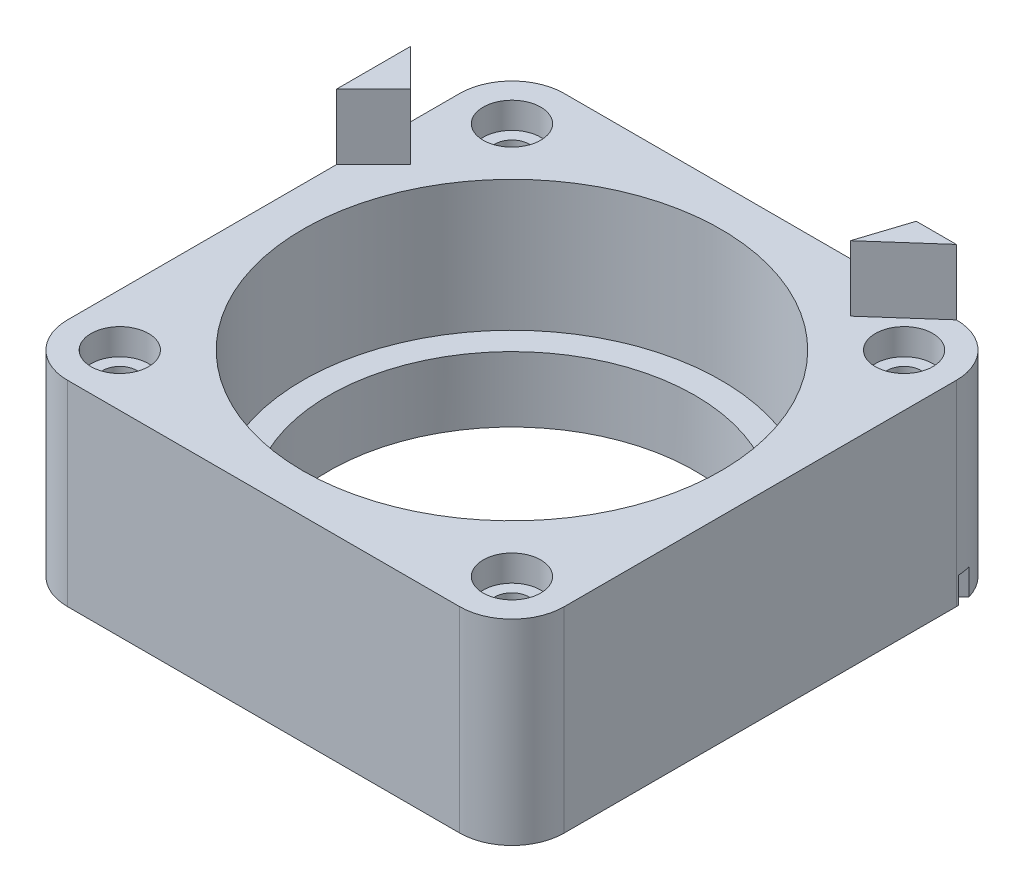
SolidWorks part; units mm, degrees
material "ABS"
ref_plane "Front Plane" through (0, 0, 0) normal (0, 0, 1) x (1, 0, 0)
ref_plane "Top Plane" through (0, 0, 0) normal (0, 1, 0) x (1, 0, 0)
ref_plane "Right Plane" through (0, 0, 0) normal (1, 0, 0) x (0, 0, -1)
sketch "Sketch1" plane through (0, 0, 0) normal (0, 1, 0) x (1, 0, 0)
  line L0 (19, 19) -> (-19, 19)
  line L1 (-19, 19) -> (-19, -19)
  line L2 (-19, -19) -> (19, -19)
  line L3 (19, -19) -> (19, 19)
  line L4 (-19, 19) -> (19, -19) construction
  line L5 (-19, -19) -> (19, 19) construction
  point P0 (0, 0)
  dimension "D2" = 38
  dimension "D3" = 38
extrude "Boss-Extrude1" add sketch "Sketch1" along normal blind 15
ref_axis "Axis1" through (0, 15.75, 0) along (0, -1, 0)
sketch "Sketch2" plane through (0, 15, 0) normal (0, 1, 0) x (1, 0, 0)
  circle A0 centre (0, 0) radius 16
  circle A1 centre (0, 0) radius 14
  dimension "D1" = 32
  dimension "D2" = 28
extrude "Cut-Extrude1" cut sketch "Sketch2" against normal blind 10 contours A0
extrude "Cut-Extrude3" cut sketch "Sketch2<3>" against normal through all contours A1 region at (0, 15, 0)
sketch "Sketch2<3>" plane through (0, 15, 0) normal (0, 1, 0) x (1, 0, 0) same geometry as "Sketch2"
sketch "Sketch3" plane through (0, 15, 0) normal (0, 1, 0) x (1, 0, 0)
  line L0 (0, 0) -> (-19, 19) construction
  line L1 (0, -7.0062) -> (0, 23.389) construction
  line L2 (-19, 6.2721) -> (-15.4645, 9.8076)
  line L3 (-19, 19) -> (-19, -19) construction
  line L4 (-15.4645, 9.8076) -> (-19, 13.3431)
  line L5 (-19, 13.3431) -> (-19, 6.2721)
  line L6 (0, 0) -> (8.7986, 31.7269) construction
  line L7 (9.4201, 19) -> (8.0839, 14.1818)
  line L8 (19, 19) -> (-19, 19) construction
  line L9 (8.0839, 14.1818) -> (12.9021, 12.8457)
  line L10 (12.9021, 12.8457) -> (9.4201, 19)
  point P16 (8.752, 16.5909)
  dimension "D1" = 4
  dimension "D2" = 5
  dimension "D3" = 15.5
  dimension "D4" = 5
  dimension "D5" = 5
  dimension "D6" = 4
extrude "Boss-Extrude2" [suppressed] add sketch "Sketch3" along normal blind 6 contours L4 L5 L2 | L9 L10 L7
mirror "Mirror1" [suppressed] about plane through (0, 0, 0) normal (1, 0, 0)
fillet "Fillet1" radius 4 4 edges at (-19, 7.5, 19) (19, 7.5, 19) (-19, 7.5, -19) (19, 7.5, -19)
hole_wizard "CBORE for M2 SHCS1" positions "Sketch4" profile "Sketch5" counterbore size "M2" standard "ANSI Metric" end condition through all
sketch "Sketch4" plane through (0, 15, 0) normal (0, 1, 0) x (1, 0, 0)
  point P0 (-15, 15)
  point P3 (15, 15)
  point P6 (-15, -15)
  point P9 (15, -15)
sketch "Sketch5" plane through (-15, 15, -15) normal (1, 0, 0) x (0, 0, 1)
  line L0 (0, 0) -> (0, 15)
  line L1 (0, 15) -> (1.3, 15)
  line L3 (1.3, 15) -> (1.3, 2)
  line L4 (1.3, 2) -> (2.2, 2)
  line L5 (2.2, 2) -> (2.2, 0)
  line L7 (2.2, 0) -> (0, 0)
  line L11 (0, -6.35) -> (0, 107.95) construction
  dimension "Thru Hole Dia." = 2.6
  dimension "Thru Hole Depth" = 15
  dimension "C'Bore Dia." = 4.4
  dimension "C'Bore Depth" = 2
sketch "Sketch6" plane through (0, 0, 0) normal (0, -1, 0) x (1, 0, 0)
  line L0 (0, 0) -> (0, -14) construction
  line L1 (0.3436, 2.4763) -> (0.481, 3.4668)
  line L2 (0, 0) -> (9.872, -9.9269) construction
  line L3 (0.481, 3.4668) -> (19, -15.1553)
  line L4 (19, 15) -> (19, -15) construction
  line L5 (19, -15.1553) -> (19, -16.284)
  line L6 (19, -16.284) -> (0.3436, 2.4763)
  circle A0 centre (0, 0) radius 14 construction
  circle A1 centre (0, 0) radius 2.5 construction
  circle A2 centre (0, 0) radius 3.5 construction
  dimension "D2" = 7
  dimension "D3" = 1
  dimension "D1" = 315.159
extrude "Cut-Extrude4" cut sketch "Sketch6" against normal blind 2
fillet "Fillet2" [suppressed] radius 1
sketch "Sketch7" plane through (0, 15, 0) normal (0, 1, 0) x (1, 0, 0)
  line L0 (0, 0) -> (-19.6843, 19.6843) construction
  line L1 (-19, 11.2218) -> (-16.1716, 8.3934)
  line L2 (-19, 15) -> (-19, -15) construction
  line L3 (-16.1716, 8.3934) -> (-19, 5.565)
  line L4 (11.9326, 19) -> (10.7005, 15.1945)
  line L5 (-19, 5.565) -> (-19, 11.2218)
  line L6 (-24.9366, 0) -> (31.9484, 0) construction
  line L7 (0, 0) -> (6.1515, 19) construction
  line L8 (0, 0) -> (0, 22.6929) construction
  line L9 (15, 19) -> (-15, 19) construction
  line L10 (10.7005, 15.1945) -> (15, 19)
  line L11 (15, 19) -> (11.9326, 19)
  circle A1 centre (0, 0) radius 18.1 construction
  dimension "D9" = 36.2
  dimension "D1" = 5.5
  dimension "D2" = 45
  dimension "D3" = 4
  dimension "D4" = 5.5
  dimension "D5" = 17.94
  dimension "D6" = 4
extrude "Boss-Extrude3" add sketch "Sketch7" along normal blind 5
